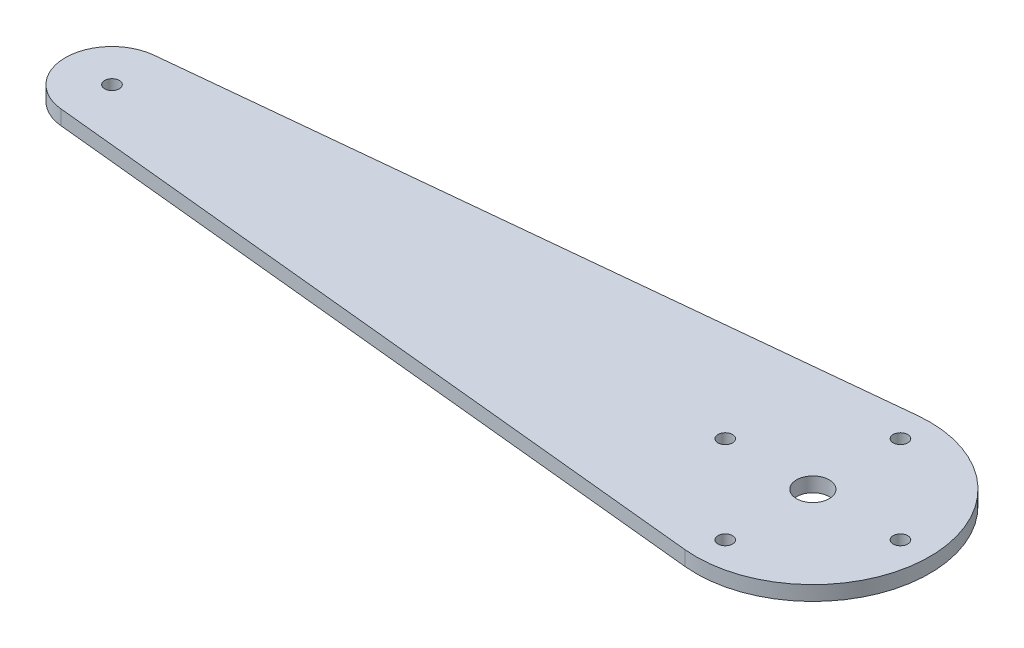
SolidWorks part; units mm, degrees
ref_plane "Front Plane" through (0, 0, 0) normal (0, 0, 1) x (1, 0, 0)
ref_plane "Top Plane" through (0, 0, 0) normal (0, 1, 0) x (1, 0, 0)
ref_plane "Right Plane" through (0, 0, 0) normal (1, 0, 0) x (0, 0, -1)
sketch "Sketch1" plane through (0, 0, 0) normal (0, 1, 0) x (1, 0, 0)
  line L0 (-153.416, 10.1091) -> (-2.54, 25.2727)
  line L1 (-153.416, -10.1091) -> (-2.54, -25.2727)
  line L2 (-111.3601, 0) -> (-50111.3601, 0) construction
  line L3 (0, -984.3615) -> (0, 49015.6385) construction
  line L4 (0, 0) -> (0, 19.05) construction
  line L5 (0, 0) -> (19.05, 0) construction
  arc A0 (-2.54, -25.2727) -> (-2.54, 25.2727) centre (0, 0) ccw
  arc A1 (-153.416, 10.1091) -> (-153.416, -10.1091) centre (-152.4, 0) ccw
  circle A2 centre (-152.4, 0) radius 1.5875
  circle A3 centre (0, 0) radius 3.556
  circle A4 centre (0, 19.05) radius 1.5875
  circle A5 centre (19.05, 0) radius 1.5875
  circle A6 centre (0, -19.05) radius 1.5875
  circle A7 centre (-19.05, 0) radius 1.5875
  dimension "D1" = 10.16
  dimension "D2" = 25.4
  dimension "D4" = 3.175
  dimension "D5" = 7.112
  dimension "D6" = 3.175
  dimension "D3" = 152.4
  dimension "D7" = 19.05
  dimension "D9" = 90
  dimension "D10" = 19.05
  dimension "D8" = 4
extrude "Boss-Extrude1" add sketch "Sketch1" along normal blind 3.175
